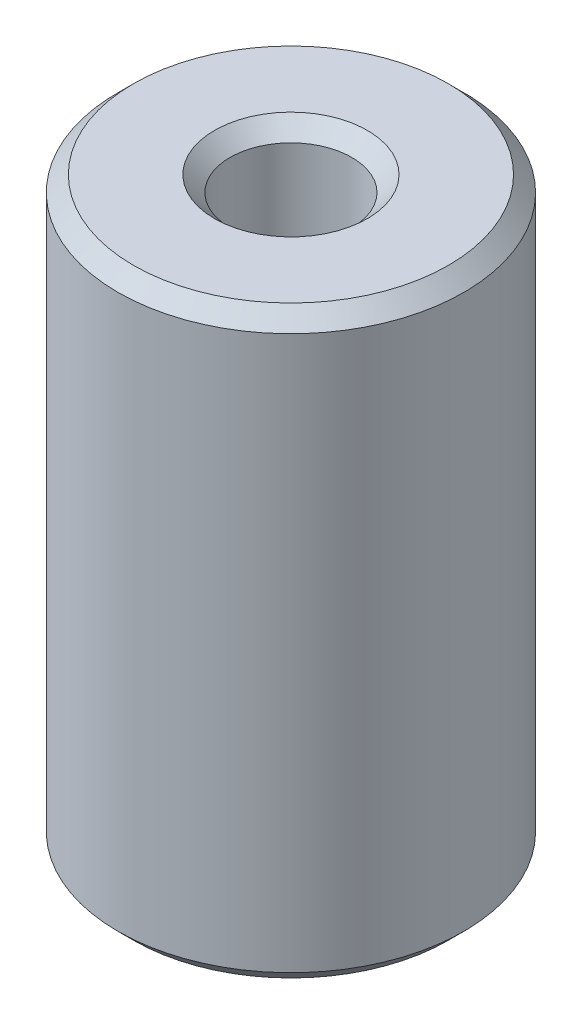
SolidWorks part; units mm, degrees
ref_plane "Front Plane" through (0, 0, 0) normal (0, 0, 1) x (1, 0, 0)
ref_plane "Top Plane" through (0, 0, 0) normal (0, 1, 0) x (1, 0, 0)
ref_plane "Right Plane" through (0, 0, 0) normal (1, 0, 0) x (0, 0, -1)
sketch "Sketch1" plane through (0, 0, 0) normal (0, 1, 0) x (1, 0, 0)
  circle A0 centre (0, 0) radius 5
  dimension "SLEEVE_OD" = 10
extrude "Boss-Extrude1" add sketch "Sketch1" along normal blind 16.8949
sketch "Sketch2" plane through (0, 0, 0) normal (0, 1, 0) x (1, 0, 0)
  circle A0 centre (0, 0) radius 1.7593
  dimension "BORE_D" = 3.5186
extrude "Cut-Extrude1" cut sketch "Sketch2" along normal through all
chamfer "Chamfer1" distance 0.4504 angle 45 4 edges at (0, 16.8949, 1.7593) (0, 0, 1.7593) (0, 0, 5) (0, 16.8949, 5)
